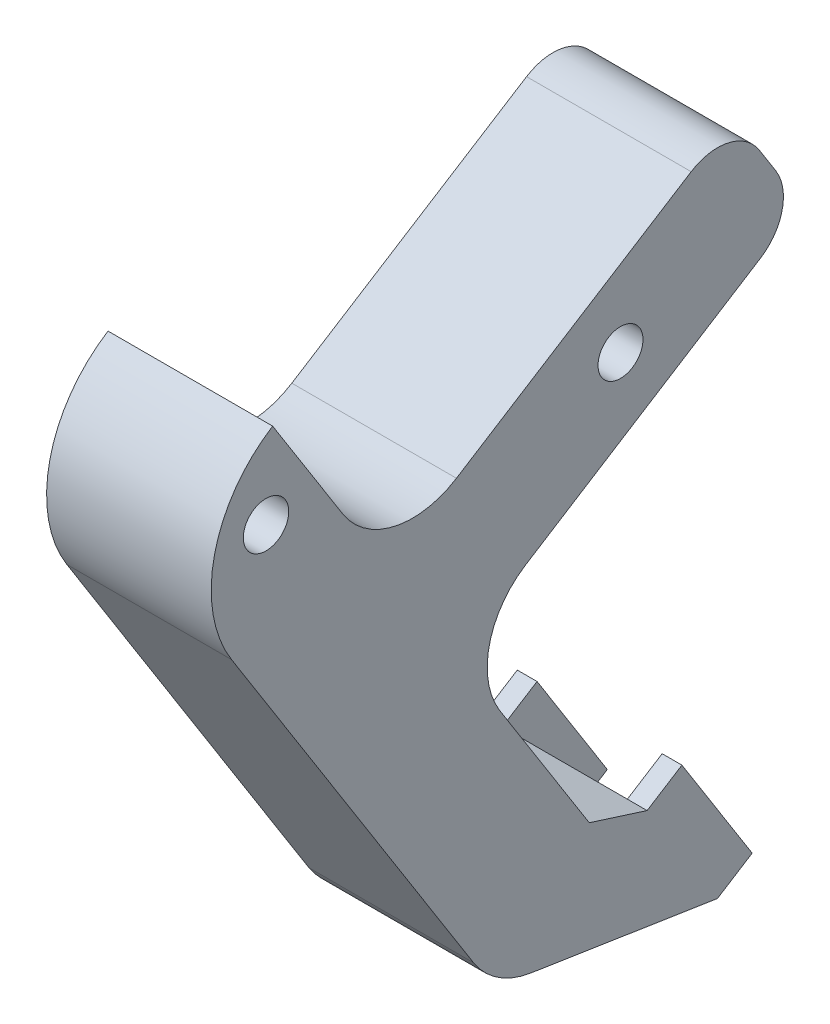
SolidWorks part; units mm, degrees
ref_plane "Front Plane" through (0, 0, 0) normal (0, 0, 1) x (1, 0, 0)
ref_plane "Top Plane" through (0, 0, 0) normal (0, 1, 0) x (1, 0, 0)
ref_plane "Right Plane" through (0, 0, 0) normal (1, 0, 0) x (0, 0, -1)
sketch "Sketch2" plane through (0, 13820.708, 11763.1576) normal (1, 0, 0) x (0, 0.8457, 0.5336)
  line L7 (77.8201, 2.6981) -> (77.8201, -12.0456)
  line L9 (81.6301, -15.8556) -> (84.0116, -15.8556)
  line L10 (87.8216, -12.0456) -> (87.8216, 2.6981)
  line L14 (44.8152, 12.7) -> (53.5835, 12.7)
  line L15 (56.0393, 13.5971) -> (58.5541, 15.7172)
  line L16 (58.5541, 15.7172) -> (71.4701, 15.7172)
  line L19 (77.8201, 9.3672) -> (77.8201, 2.6981)
  line L21 (44.8152, 12.7) -> (54.386, 23.6962)
  line L25 (87.8216, 9.3672) -> (87.8216, 2.6981)
  line L26 (56.0393, 13.5971) -> (54.9752, 12.7)
  line L27 (54.9752, 12.7) -> (53.5835, 12.7)
  line L28 (59.1758, 25.8772) -> (104.3286, 25.8772)
  line L29 (104.3286, 25.8772) -> (104.3286, 15.7172)
  line L30 (104.3286, 15.7172) -> (94.1716, 15.7172)
  circle A0 centre (82.8208, -2.4426) radius 1.7339
  arc A1 (94.1716, 15.7172) -> (87.8216, 9.3672) centre (94.1716, 9.3672) ccw
  arc A2 (77.8201, 9.3672) -> (71.4701, 15.7172) centre (71.4701, 9.3672) ccw
  arc A3 (77.8201, -12.0456) -> (81.6301, -15.8556) centre (81.6301, -12.0456) ccw
  arc A4 (87.8216, -12.0456) -> (84.0116, -15.8556) centre (84.0116, -12.0456) cw
  arc A6 (54.386, 23.6962) -> (59.1758, 25.8772) centre (59.1758, 19.5272) cw
  dimension "D1" = 6.35
  dimension "D2" = 6.35
  dimension "D3" = 3.81
  dimension "D4" = 3.81
  dimension "D6" = 6.35
extrude "Boss-Extrude1" add sketch "Sketch2" along normal blind 6.35 and the other way blind 6.35
fillet "Fillet1" radius 10.16 1 edges at (0, 13895.1317, 11840.7152)
sketch "Sketch3" plane through (6.35, 0, 0) normal (1, 0, 0) x (0, -0.9762, 0.217)
  line L0 (-10987.1605, -14566.827) -> (-10994.3198, -14559.618)
  line L1 (-10994.3198, -14559.618) -> (-11001.5288, -14566.773)
  arc A0 (-11001.5288, -14566.773) -> (-10987.1626, -14566.8249) centre (-10994.3198, -14559.618) ccw
sketch "Sketch5" plane through (0, -1379.9041, 2186.931) normal (0, 0.5336, -0.8457) x (-1, 0, 0)
  line L1 (6.35, 18010.4091) -> (-6.35, 18010.4091) construction
  line L4 (6.35, 18020.5691) -> (-6.35, 18020.5691) construction
  line L5 (1839.6239, 18020.5691) -> (1839.6239, 18010.4091)
  line L9 (1851.8803, 18020.5691) -> (1848.9925, 18020.5691)
  line L10 (1848.9925, 18020.5691) -> (1848.9925, 18010.4091)
  line L19 (4.826, 18020.5691) -> (4.826, 18011.9804)
  line L20 (4.826, 18020.5691) -> (6.35, 18020.5691)
  line L21 (6.35, 18020.5691) -> (6.35, 18012.0257)
  line L22 (-6.35, 18011.9804) -> (-6.35, 18020.5691)
  line L23 (-6.35, 18020.5691) -> (-4.826, 18020.5691)
  line L24 (-4.826, 18020.5691) -> (-4.826, 18011.9804)
  line L25 (-4.826, 18011.9804) -> (-4.826, 18010.4091)
  line L26 (-4.826, 18010.4091) -> (-6.35, 18010.4091)
  line L27 (-6.35, 18010.4091) -> (-6.35, 18011.9804)
  line L28 (4.826, 18011.9804) -> (4.826, 18010.4091)
  line L29 (4.826, 18010.4091) -> (6.35, 18010.4091)
  line L30 (6.35, 18010.4091) -> (6.35, 18012.0257)
  line M1 (6.35, 18020.5691) -> (-6.35, 18020.5691)
  line M2 (-6.35, 18020.5691) -> (-6.35, 18010.4091)
  line M3 (-6.35, 18010.4091) -> (6.35, 18010.4091)
  line M4 (6.35, 18010.4091) -> (6.35, 18020.5691)
extrude "Boss-Extrude3" add sketch "Sketch5" along normal blind 3.175 contours L5 M1 M2 M3 | L10 M1 M3 M4 region at (-5.588, 13856.1282, 11800.5238) region at (5.588, 13856.1282, 11800.5238)
sketch "Sketch7" plane through (6.35, 0, 0) normal (1, 0, 0) x (0, 0, -1)
  circle A0 centre (-11832.6349, 13894.2253) radius 1.7526
extrude "Cut-Extrude3" cut sketch "Sketch7" against normal blind 22.606
